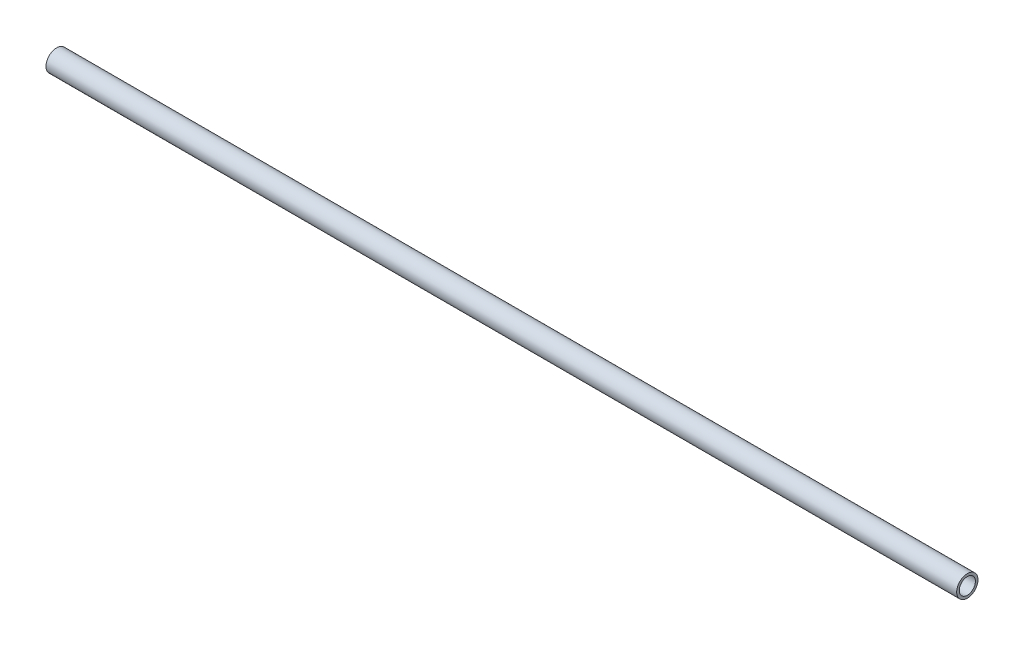
SolidWorks part; units mm, degrees
ref_plane "Front Plane" through (0, 0, 0) normal (0, 0, 1) x (1, 0, 0)
ref_plane "Top Plane" through (0, 0, 0) normal (0, 1, 0) x (1, 0, 0)
ref_plane "Right Plane" through (0, 0, 0) normal (1, 0, 0) x (0, 0, -1)
ref_axis "Axis1" through (-4.5, 0, 0) along (1, 0, 0)
sketch "Sketch1" plane through (0, 0, 0) normal (1, 0, 0) x (0, 0, -1)
  circle A0 centre (0, 0) radius 0.8001
  circle A1 centre (0, 0) radius 1.0541
  dimension "D1" = 1.6002
  dimension "D2" = 2.1082
extrude "Boss-Extrude1" add sketch "Sketch1" along normal blind 90
sketch "Sketch2" plane through (0, 0, 0) normal (-1, 0, 0) x (0, 0, 1)
  line L0 (0, 0) -> (0, 0.6106) construction
  line L2 (-0.304, 0.6106) -> (-0.304, 1.0992)
  line L3 (-0.304, 1.0992) -> (0.304, 1.0992)
  line L4 (0.304, 1.0992) -> (0.304, 0.6106)
  arc A0 (-0.304, 0.6106) -> (0.304, 0.6106) centre (0, 0.6106) ccw
  dimension "D1" = 0.608
extrude "Cut-Extrude1" [suppressed] cut sketch "Sketch2" against normal blind 1
sketch "Sketch3" plane through (0, 0, 0) normal (0, 0, 1) x (1, 0, 0)
  circle A0 centre (0.7986, 0) radius 0.3969
  dimension "D1" = 0.7937
extrude "Cut-Extrude2" cut sketch "Sketch3" against normal blind 10
equation "\"Do\"=8.5mm"
equation "\"Lo\"=10"
equation "\"screw_diam\" = 3.5mm"
equation "\"wheel_Do\"=12.5mm"
equation "\"wheel_thickness\"=4mm"
equation "\"Collet_diameter\"=4.3"
equation "\"clearance\"= 0.5mm"
equation "\"handle_body_width\" = 10mm"
equation "\"finger_diameter\"=35"
equation "\"collet_lid_diameter\"=10"
equation "\"screw_cap_diam\"=5.15"
equation "\"handle_thickness\"=12.5mm"
equation "\"post_hole_diam\"=2"
equation "\"roll_rod_diam\"= 6.5 "
equation "\"roll_rod_length\"=6.6"
equation "\"disc_diam\"=5"
equation "\"disc_width\"=1.5"
equation "\"arm_width\"=5"
equation "\"arm_thickness\"=4.5"
equation "\"wheel_total_diam\"=30"
equation "\"spring_diam\"=4.1"
equation "\"collet_length\" = 18.75mm"
equation "\"tip_length\" = 40mm"
equation "\"cable_tube_OD\"=0.508"
equation "\"D1@Sketch2\"=\"cable_tube_OD\"+0.1"
